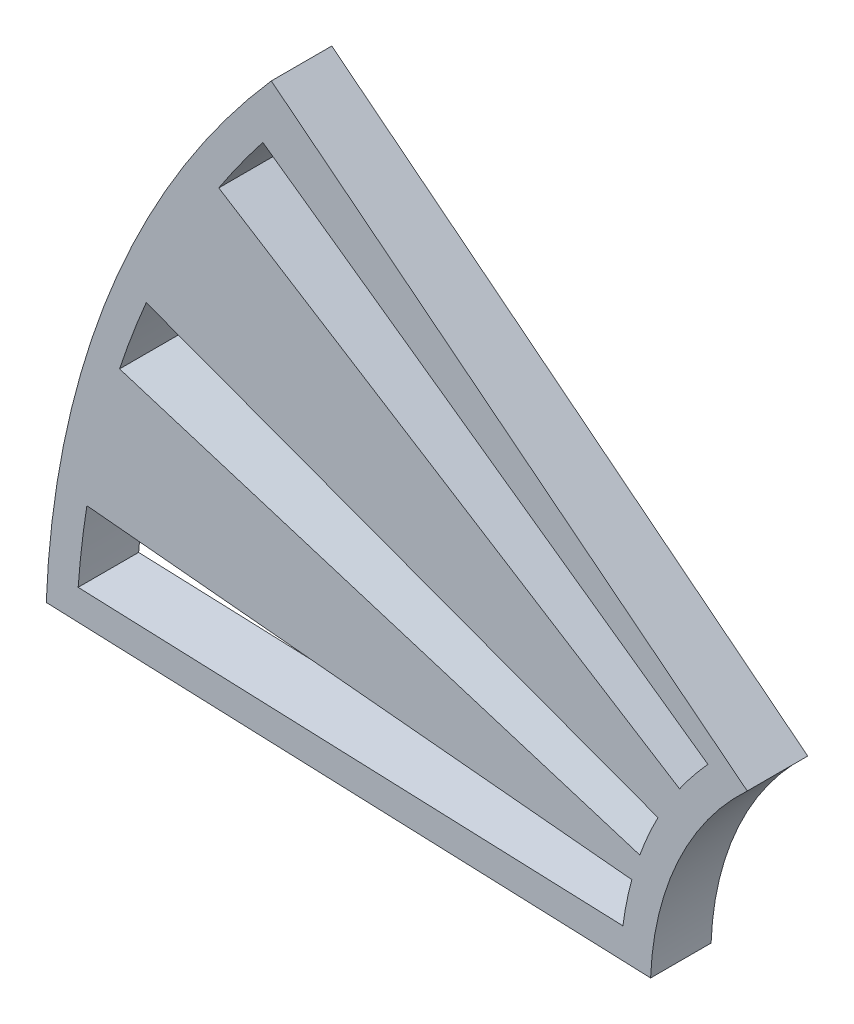
SolidWorks part; units mm, degrees
ref_plane "Front Plane" through (0, 0, 0) normal (0, 0, 1) x (1, 0, 0)
ref_plane "Top Plane" through (0, 0, 0) normal (0, 1, 0) x (1, 0, 0)
ref_plane "Right Plane" through (0, 0, 0) normal (1, 0, 0) x (0, 0, -1)
sketch "Sketch1" plane through (0, 0, 0) normal (0, 0, 1) x (1, 0, 0)
  line L0 (-19.9854, 0.7628) -> (-59.9563, 2.2884)
  line L1 (-16.3569, 14.7123) -> (-16.1915, 14.8941)
  line L2 (0, 0) -> (-50.7795, 31.96) construction
  line L3 (0, 0) -> (-57.3211, 17.7283) construction
  line L4 (-21.8167, 2.8342) -> (-57.8471, 4.2094)
  line L5 (-13.5925, 14.6712) -> (-45.0737, 39.6026)
  line L6 (-21.2283, 5.7759) -> (-57.2696, 9.1759)
  line L7 (-57.0177, 18.6812) -> (-57.0256, 18.6836)
  line L8 (-20.7005, 7.449) -> (-55.1067, 18.0901)
  line L9 (-19.4947, 10.196) -> (-53.3439, 22.7691)
  line L10 (-18.0672, 12.5529) -> (-48.5469, 31.7364)
  line L11 (-50.2398, 32.8019) -> (-50.2468, 32.8063)
  line L12 (0.5327, 0.8463) -> (-50.2468, 32.8063) construction
  line L13 (-16.1915, 14.8941) -> (-45.6332, 35.7997)
  line L15 (-16.3569, 14.7123) -> (-40.8618, 41.162) construction
  line L16 (-13.5925, 14.6712) -> (-40.7774, 44.0137) construction
  arc A0 (-45.0737, 39.6026) -> (-59.9563, 2.2884) centre (0, 0) ccw
  arc A1 (-13.5925, 14.6712) -> (-19.9854, 0.7628) centre (0, 0) ccw
  arc A2 (-45.6332, 35.7997) -> (-48.5469, 31.7364) centre (0, 0) ccw
  arc A3 (-16.3569, 14.7123) -> (-18.0672, 12.5529) centre (0, 0) ccw
  arc A4 (-53.3439, 22.7691) -> (-55.1067, 18.0901) centre (0, 0) ccw
  arc A5 (-40.8618, 41.162) -> (-57.8471, 4.2094) centre (0, 0) ccw construction
  arc A6 (-19.4947, 10.196) -> (-20.7005, 7.449) centre (0, 0) ccw
  arc A7 (-21.2283, 5.7759) -> (-21.8167, 2.8342) centre (0, 0) ccw
  arc A8 (-16.3569, 14.7123) -> (-21.8167, 2.8342) centre (0, 0) ccw construction
  arc A9 (-57.2696, 9.1759) -> (-57.8471, 4.2094) centre (0, 0) ccw
  arc A11 (-40.7774, 44.0137) -> (-59.9563, 2.2884) centre (0, 0) ccw construction
  point P16 (0.2955, 0.9554)
  dimension "D1" = 120
  dimension "D2" = 40
  dimension "D3" = 0.2459
  dimension "D4" = 15
  dimension "D5" = 2
  dimension "15" = 15
  dimension "D6" = 3
  dimension "D7" = 5
  dimension "D8" = 3
  dimension "D9" = 5
  dimension "D11" = 3
  dimension "D12" = 5
  dimension "D13" = 3
  dimension "D10" = 1
extrude "Boss-Extrude2" add sketch "Sketch1" along normal blind 4 contours L0 A0 L5 A1
extrude "Cut-Extrude1" cut sketch "Sketch1<5>" along normal through all contours A6 L9 A4 L8 | L6 A9 L4 A7 | A3 L1 L13 A2 L10 | L4 A9 L6 A7 | L8 A4 L9 A6 region at (-33.393, 24.6066, 0) region at (-41.0968, 5.6048, 0) region at (-38.6238, 15.1254, 0)
sketch "Sketch1<5>" plane through (0, 0, 0) normal (0, 0, 1) x (1, 0, 0) same geometry as "Sketch1"
ref_plane "Plane1" through (-19.9854, 0.7628, 4) normal (-0.0381, -0.9993, 0) x (-0.9993, 0.0381, 0)
